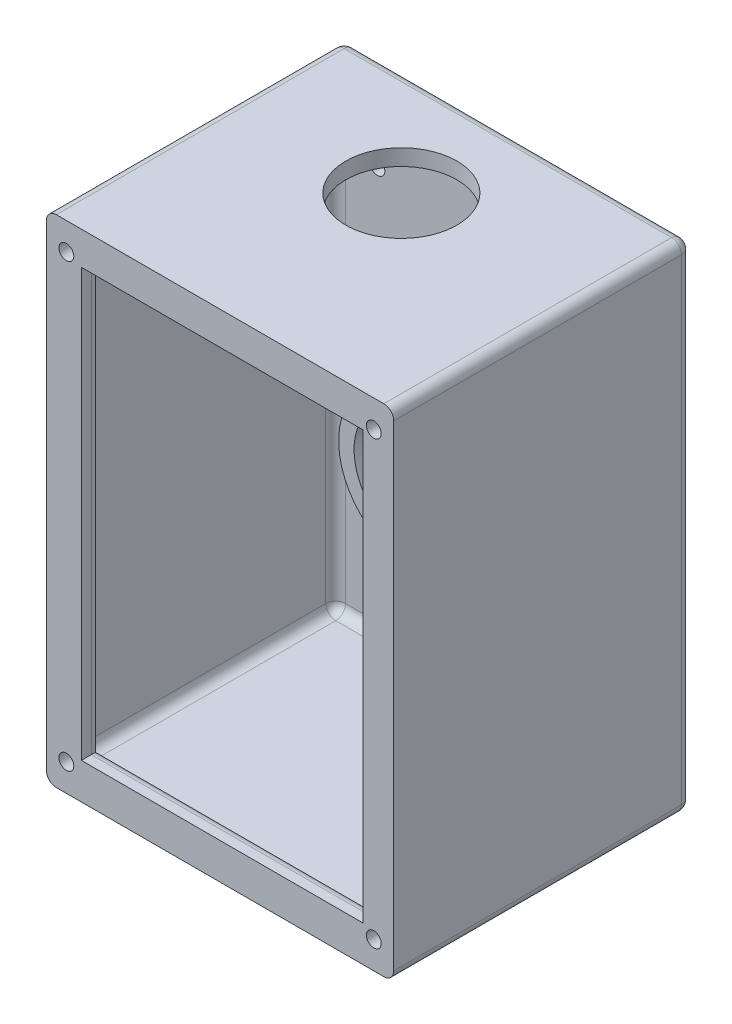
SolidWorks part; units mm, degrees
ref_plane "Plano frontal" through (0, 0, 0) normal (0, 0, 1) x (1, 0, 0)
ref_plane "Plano superior" through (0, 0, 0) normal (0, 1, 0) x (1, 0, 0)
ref_plane "Plano direito" through (0, 0, 0) normal (1, 0, 0) x (0, 0, -1)
sketch "Esboço1" plane through (0, 0, 0) normal (0, 0, 1) x (1, 0, 0)
  line L0 (-29.1211, -32.4382) -> (40.8789, -32.4382) construction
  line L1 (-29.1211, 17.5618) -> (40.8789, 17.5618)
  line L2 (-29.1211, 17.5618) -> (-29.1211, -82.4382)
  line L3 (-29.1211, -82.4382) -> (40.8789, -82.4382)
  line L4 (40.8789, 17.5618) -> (40.8789, -82.4382)
  line L5 (5.8789, 17.5618) -> (5.8789, -82.4382) construction
  circle A0 centre (5.8789, -32.4382) radius 12
  dimension "D3" = 24
  dimension "D1" = 70
  dimension "D2" = 100
extrude "Ressalto-extrusão1" add sketch "Esboço1" along normal blind 4
sketch "Esboço2" plane through (0, 0, 0) normal (0, 0, 1) x (1, 0, 0)
  circle A0 centre (5.8789, -32.4382) radius 12
  circle A1 centre (5.8789, -32.4382) radius 15.1029
extrude "Ressalto-extrusão2" add sketch "Esboço2" along normal blind 21
sketch "Esboço3" plane through (0, 0, 0) normal (0, 0, 1) x (1, 0, 0)
  line L0 (-29.1211, 17.5618) -> (40.8789, -82.4382) construction
  line L1 (-29.1211, 17.5618) -> (40.8789, 17.5618)
  line L2 (-29.1211, 17.5618) -> (-29.1211, -82.4382)
  line L3 (-29.1211, -82.4382) -> (40.8789, -82.4382)
  line L4 (40.8789, 17.5618) -> (40.8789, -82.4382)
  line L6 (-26.8272, 14.2849) -> (38.5851, 14.2849)
  line L7 (-26.8272, 14.2849) -> (-26.8272, -79.1612)
  line L8 (-26.8272, -79.1612) -> (38.5851, -79.1612)
  line L9 (38.5851, 14.2849) -> (38.5851, -79.1612)
  dimension "D1" = 4
  dimension "D2" = 4
extrude "Ressalto-extrusão3" add sketch "Esboço3" along normal blind 60
fillet "Filete1" radius 2 1 edges at (-29.1211, -32.4382, 0)
fillet "Filete2" radius 2 1 edges at (40.8789, -32.4382, 0)
fillet "Filete3" radius 2 1 edges at (-26.8272, -32.4382, 4)
fillet "Filete4" radius 2 4 edges at (-26.8272, -79.1612, 33) (-26.2414, -79.1612, 4.5858) (6.8789, -79.1612, 4) (38.5851, -32.4382, 4)
fillet "Filete5" radius 2 5 edges at (-26.8272, 14.2849, 33) (-26.2414, 14.2849, 4.5858) (38.5851, 14.2849, 33) (37.9993, 14.2849, 4.5858) (5.8789, 14.2849, 4)
sketch "Esboço4" plane through (0, 0, 0) normal (0, 0, 1) x (1, 0, 0)
  line L0 (-29.1211, 17.5618) -> (40.8789, -82.4382) construction
  line L1 (40.8789, -82.4382) -> (-29.1211, -82.4382) construction
  line L2 (-29.1211, -82.4382) -> (40.8789, 17.5618) construction
  circle A0 centre (-18.4139, 2.2659) radius 1.5
  circle A1 centre (30.1717, 2.2659) radius 1.5
  circle A2 centre (30.1717, -67.1422) radius 1.5
  circle A3 centre (-18.4139, -67.1422) radius 1.5
  dimension "D1" = 3
  dimension "D2" = 3
  dimension "D3" = 3
  dimension "D4" = 3
extrude "Corte-extrusão1" cut sketch "Esboço4" along normal blind 17 and the other way blind 14
fillet "Filete6" radius 2 5 edges at (40.8789, 17.5618, 31) (40.2931, 17.5618, 0.5858) (5.8789, 17.5618, 0) (-28.5353, 17.5618, 0.5858) (-29.1211, 17.5618, 31)
fillet "Filete7" radius 2 5 edges at (-28.5353, -82.4382, 0.5858) (5.8789, -82.4382, 0) (40.2931, -82.4382, 0.5858) (-29.1211, -82.4382, 31) (40.8789, -82.4382, 31)
sketch3d "3DSketch1"
  line L0 (-27.1211, -82.4382, 60) -> (38.8789, -82.4382, 60) construction
  line L1 (-29.1211, 15.5618, 60) -> (-29.1211, -80.4382, 60) construction
  line L2 (-26.8272, -78.6488, 60) -> (-26.8272, -81.0398, 60)
  line L3 (-26.8272, 15.9023, 60) -> (39.439, 15.9023, 60)
  line L4 (-26.8272, 15.9023, 60) -> (-26.8272, 15.5618, 60)
  line L5 (-26.8272, -81.0398, 60) -> (39.439, -81.0398, 60)
  line L6 (39.439, 15.9023, 60) -> (39.439, -81.0398, 60)
  line L7 (-22.0736, 10.9031, 60) -> (34.6571, 10.9031, 60)
  line L8 (-22.0736, 10.9031, 60) -> (-22.0736, -75.1711, 60)
  line L9 (-22.0736, -75.1711, 60) -> (34.6571, -75.1711, 60)
  line L10 (34.6571, 10.9031, 60) -> (34.6571, -75.1711, 60)
  line L11 (-29.1211, 15.5618, 60) -> (-26.8272, 15.5618, 60)
  line L12 (-29.1211, 15.5618, 60) -> (-29.1211, -78.6488, 60)
  line L13 (-29.1211, -78.6488, 60) -> (-26.8272, -78.6488, 60)
extrude "Ressalto-extrusão4" add sketch "3DSketch1" along direction (0, 0, 1) on the side against the normal blind 4
sketch "Esboço5" plane through (0, 0, 60) normal (0, 0, 1) x (1, 0, 0)
  line L0 (-28.5353, 16.9761) -> (40.2931, -81.8524) construction
  line L1 (40.2931, -81.8524) -> (40.2931, 16.9761) construction
  line L2 (40.2931, 16.9761) -> (-28.5353, -81.8524) construction
  arc A0 (-27.1211, 17.5618) -> (-29.1211, 15.5618) centre (-27.1211, 15.5618) ccw construction
  arc A1 (38.8789, -82.4382) -> (40.8789, -80.4382) centre (38.8789, -80.4382) ccw construction
  arc A2 (40.8789, 15.5618) -> (38.8789, 17.5618) centre (38.8789, 15.5618) ccw construction
  arc A3 (-29.1211, -80.4382) -> (-27.1211, -82.4382) centre (-27.1211, -80.4382) ccw construction
  circle A4 centre (-25.1063, 12.0524) radius 1.5
  circle A5 centre (36.8641, -76.9288) radius 1.5
  circle A6 centre (36.8641, 12.0524) radius 1.5
  circle A7 centre (-25.1063, -76.9288) radius 1.5
  dimension "D3" = 3
  dimension "D4" = 3
  dimension "D5" = 3
  dimension "D8" = 3
  dimension "D1" = 6
  dimension "D2" = 6
  dimension "D6" = 6
  dimension "D7" = 6
extrude "Corte-extrusão2" cut sketch "Esboço5" against normal blind 14 and the other way blind 4
fillet "Filete8" radius 2 4 edges
sketch "Esboço6" plane through (0, 0, 0) normal (0, 1, 0) x (1, 0, 0)
  circle A0 centre (3.8789, -21.4625) radius 11.2
  dimension "D1" = 22.4
  dimension "D2" = 35
extrude "Corte-extrusão10" cut sketch "Esboço6" against normal blind 22 and the other way blind 32
